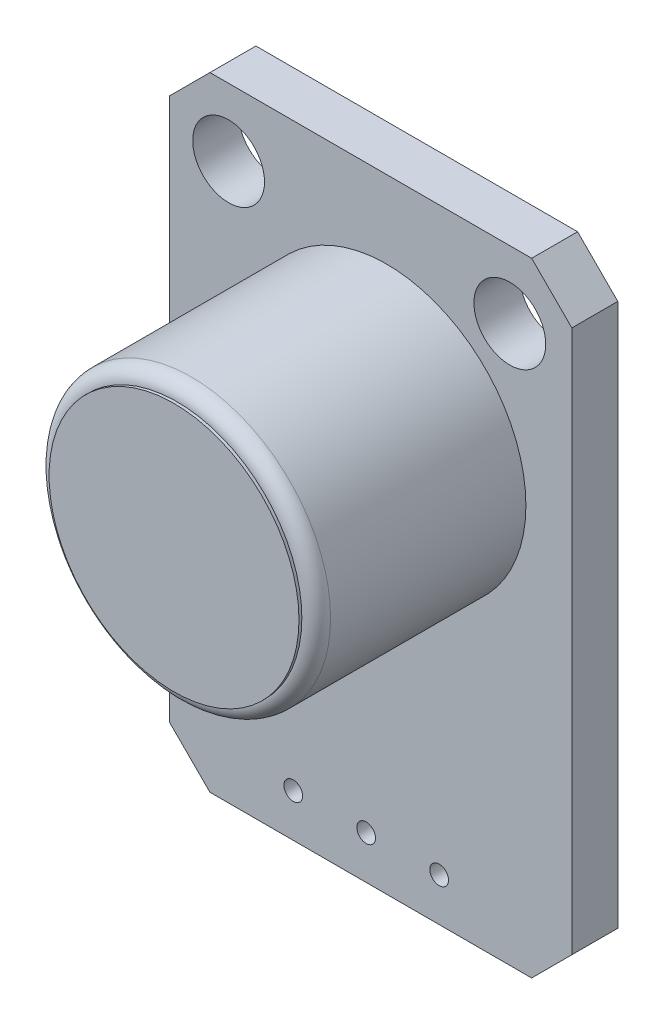
SolidWorks part; units mm, degrees
ref_plane "Front Plane" through (0, 0, 0) normal (0, 0, 1) x (1, 0, 0)
ref_plane "Top Plane" through (0, 0, 0) normal (0, 1, 0) x (1, 0, 0)
ref_plane "Right Plane" through (0, 0, 0) normal (1, 0, 0) x (0, 0, -1)
sketch "Sketch1" plane through (0, 0, 0) normal (0, 0, 1) x (1, 0, 0)
  line L0 (0, 1.4) -> (1.4, 0)
  line L1 (1.4, 0) -> (12.6, 0)
  line L2 (0, 1.4) -> (0, 20.3)
  line L3 (1.4, 21.7) -> (12.6, 21.7)
  line L4 (14, 1.4) -> (14, 20.3)
  line L5 (12.6, 0) -> (14, 1.4)
  line L6 (12.6, 21.7) -> (14, 20.3)
  line L7 (0, 20.3) -> (1.4, 21.7)
  circle A0 centre (4.3, 1.5) radius 0.3255
  circle A1 centre (6.84, 1.5) radius 0.3255
  circle A2 centre (9.38, 1.5) radius 0.3255
  circle A3 centre (7.55, 14.15) radius 4.85
  circle A4 centre (11.84, 19.35) radius 1.25
  circle A5 centre (2.05, 19.35) radius 1.25
  point P0 (0, 0)
  point P1 (14, 21.7)
  point P2 (0, 21.7)
  point P3 (14, 0)
  dimension "D1" = 1.5
  dimension "D2" = 4.3
  dimension "D4" = 7.55
  dimension "D11" = 6.45
  dimension "D12" = 2.16
  dimension "D13" = 2.35
  dimension "D14" = 2.05
  dimension "D15" = 2.35
  dimension "D3" = 3
  dimension "D5" = 21.7
  dimension "D10" = 14
extrude "Boss-Extrude1" add sketch "Sketch1" along normal blind 1.6 contours A3 | L7 L2 L0 L1 L5 L4 L6 L3 A5 A4 A3 A2 A1 A0 region at (0.2582, 10.85, 0) region at (7.55, 14.15, 0)
extrude "Boss-Extrude2" add sketch "Sketch1<3>" along normal blind 7.3 from surface contours A3 region at (7.55, 14.15, 0) starting at face at (3.3, 19.35, 1.6)
sketch "Sketch1<3>" plane through (0, 0, 0) normal (0, 0, 1) x (1, 0, 0) same geometry as "Sketch1"
fillet "Fillet1" radius 0.5 1 edges at (12.4, 14.15, 8.9)
sketch "Sketch2" plane through (0, 0, 8.9) normal (0, 0, 1) x (1, 0, 0)
  circle A1 centre (7.55, 14.15) radius 4.35
  circle A2 centre (7.55, 14.15) radius 4.35
  dimension "D1" = 0
extrude "Boss-Extrude3" add sketch "Sketch2" along normal blind 0.1
